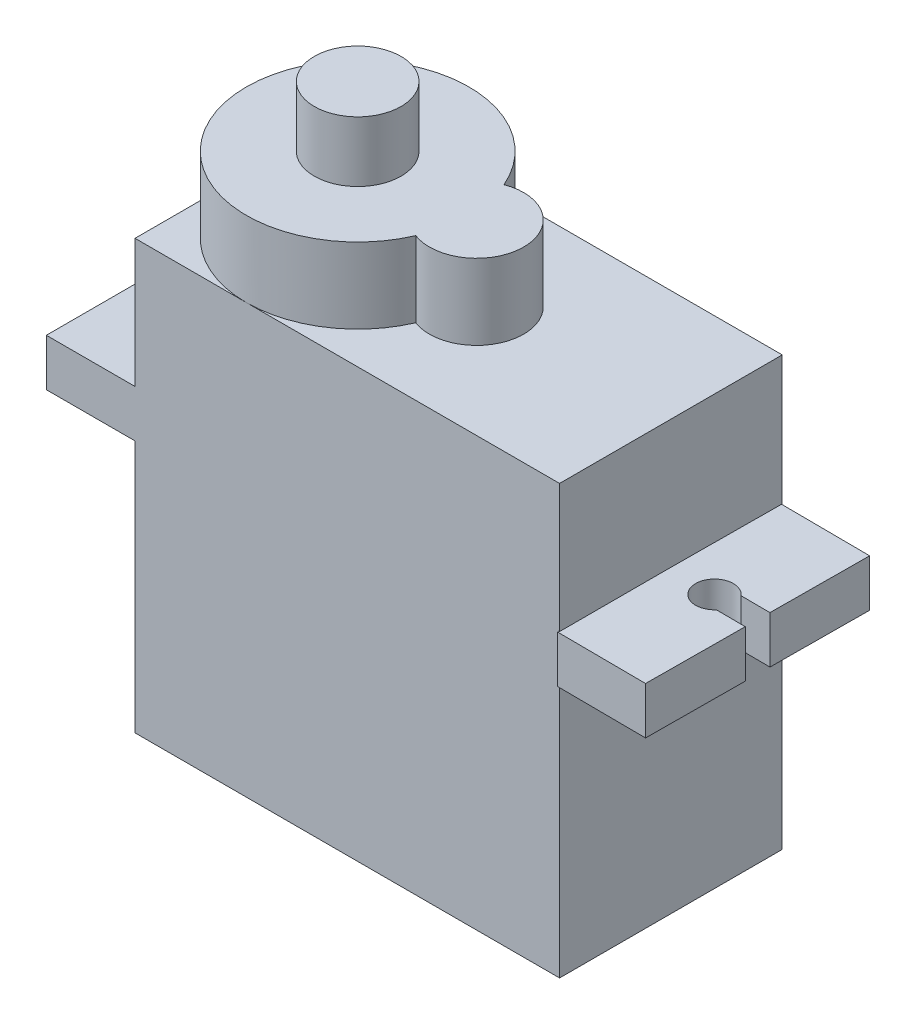
SolidWorks part; units mm, degrees
ref_plane "Alzado" through (0, 0, 0) normal (0, 0, 1) x (1, 0, 0)
ref_plane "Planta" through (0, 0, 0) normal (0, 1, 0) x (1, 0, 0)
ref_plane "Vista lateral" through (0, 0, 0) normal (1, 0, 0) x (0, 0, -1)
sketch "Croquis1" plane through (0, 0, 0) normal (0, 1, 0) x (1, 0, 0)
  line L1 (-11.25, -5.9) -> (11.25, -5.9)
  line L2 (-11.25, -5.9) -> (-11.25, 5.9)
  line L3 (-11.25, 5.9) -> (11.25, 5.9)
  line L4 (11.25, -5.9) -> (11.25, 5.9)
  line L5 (-11.25, -5.9) -> (11.25, 5.9) construction
  line L6 (-11.25, 5.9) -> (11.25, -5.9) construction
  point P0 (0, 0)
  dimension "D1" = 11.8
  dimension "D2" = 22.5
extrude "Saliente-Extruir1" add sketch "Croquis1" along normal blind 22.7
sketch "Croquis2" plane through (0, 22.7, 0) normal (0, 1, 0) x (1, 0, 0)
  line L0 (-11.25, 5.9) -> (-11.25, -5.9) construction
  line L1 (-11.25, 5.9) -> (-11.25, -5.9)
  line L2 (-11.25, -5.9) -> (-15.95, -5.9)
  line L3 (-15.95, -5.9) -> (-15.95, -0.65)
  line L4 (-15.95, 5.9) -> (-11.25, 5.9)
  line L5 (-14.4099, 0.65) -> (-15.95, 0.65)
  line L6 (-14.4099, -0.65) -> (-15.95, -0.65)
  line L7 (-15.95, 0.65) -> (-15.95, 5.9)
  line L8 (0.0667, 20.2313) -> (0, 0) construction
  line L9 (15.9885, 5.7948) -> (11.2886, 5.8257)
  line L10 (11.2886, 5.8257) -> (11.2109, -5.974)
  line L11 (11.2109, -5.974) -> (15.9108, -6.005)
  line L12 (15.9539, 0.5449) -> (15.9885, 5.7948)
  line L13 (14.4053, -0.745) -> (15.9454, -0.7551)
  line L14 (14.4139, 0.555) -> (15.9539, 0.5449)
  line L15 (15.9108, -6.005) -> (15.9454, -0.7551)
  arc A0 (0.0667, 2.3387) -> (0.0667, -2.3387) centre (-5.35, 0) ccw
  circle A1 centre (-5.35, 0) radius 2.3
  arc A2 (0.0667, -2.3387) -> (0.0667, 2.3387) centre (0.95, 0) ccw
  arc A3 (-14.4099, -0.65) -> (-14.4099, 0.65) centre (-13.65, 0) ccw
  arc A4 (14.4053, -0.745) -> (14.4139, 0.555) centre (13.6497, -0.09) cw
  point P6 (-11.25, 0)
  dimension "D1" = 5.9
  dimension "D2" = 2.3
  dimension "D3" = 2.5
  dimension "D5" = 1
  dimension "D4" = 6.3
  dimension "D6" = 2.3
  dimension "D7" = 4.7
  dimension "D8" = 5.9
extrude "Saliente-Extruir2" add sketch "Croquis2" along normal blind 4 contours A0 A2 A1 region at (-6.5059, 22.7, -5.5933)
sketch "Croquis3" plane through (0, 22.7, 0) normal (0, 1, 0) x (1, 0, 0)
  circle A0 centre (-5.35, 0) radius 2.3 construction
  circle A1 centre (-5.35, 0) radius 2.3
extrude "Saliente-Extruir3" add sketch "Croquis3" along normal blind 7.2
extrude "Saliente-Extruir4" add sketch "Croquis2<3>" against normal blind 2.5 from offset 6.8 contours L2 L3 L6 A3 L5 L7 L4 L1 | L11 L15 L13 A4 L14 L12 L9 L10 offset against normal yes
sketch "Croquis2<3>" plane through (0, 22.7, 0) normal (0, 1, 0) x (1, 0, 0) same geometry as "Croquis2"
